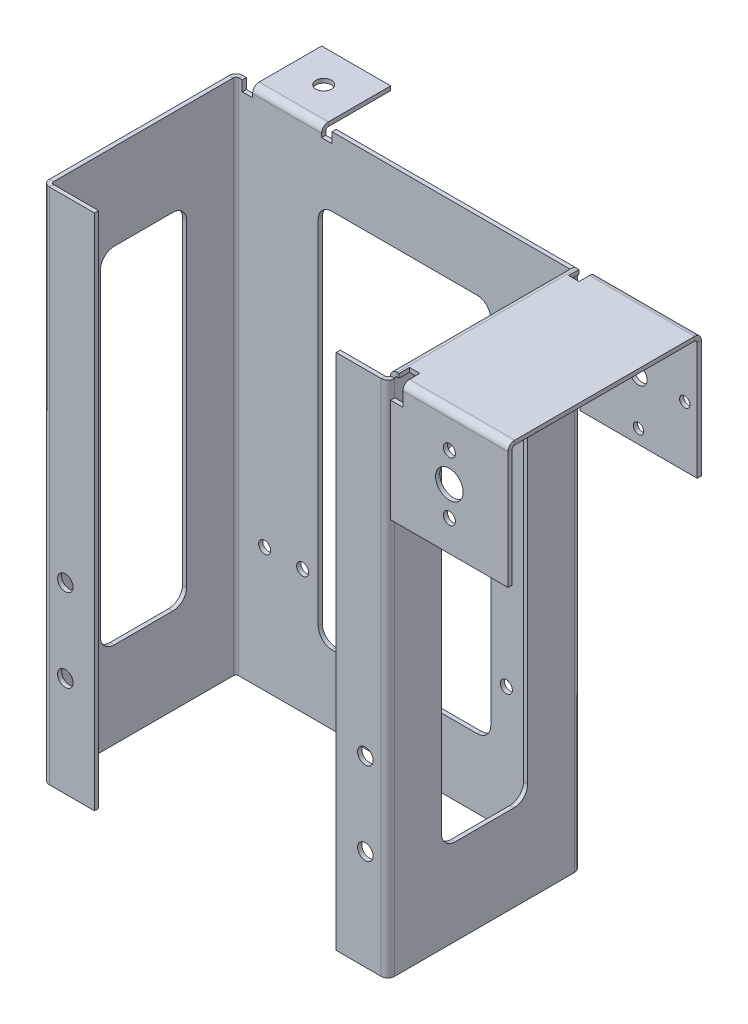
SolidWorks part; units mm, degrees
note: The reader was unsure of these and kept them because the rebuilt part matched: flange length of "Ребро-кромка1", "Ребро-кромка2", "Ребро-кромка3", "Ребро-кромка4", "Ребро-кромка5".
material "Простая углеродистая сталь"
ref_plane "Спереди" through (0, 0, 0) normal (0, 0, 1) x (1, 0, 0)
ref_plane "Сверху" through (0, 0, 0) normal (0, 1, 0) x (1, 0, 0)
ref_plane "Справа" through (0, 0, 0) normal (1, 0, 0) x (0, 0, -1)
sketch "Эскиз1" plane through (0, 0, 0) normal (0, 0, 1) x (1, 0, 0)
  line L1 (0, 0) -> (100, 0)
  line L2 (0, 0) -> (0, 150)
  line L3 (0, 150) -> (100, 150)
  line L4 (100, 0) -> (100, 150)
  dimension "D1" = 150
  dimension "D2" = 100
base flange "Базовая кромка1" sketch "Эскиз1" thickness 1.2 reverse thickness direction no parameters "D1"=0.7366
edge flange "Ребро-кромка1" sketch "Эскиз11" flange profiles "Эскиз11", "Эскиз12" flange angle 90 flange length 56 flange position material inside bend radius 0.7366 thickness 1.2 relief rectangular parameters "D6"=10, "D8"=1
sketch "Эскиз11" plane through (100, 0, 0) normal (1, 0, 0) x (0, 1, 0)
  line L2 (0, 0) -> (0, 54.8)
  line L3 (0, 54.8) -> (150, 54.8)
  line L4 (150, 54.8) -> (150, 0)
  line L5 (0, 0) -> (150, 0) construction
  line L6 (0, 0) -> (150, 0)
sketch "Эскиз12" plane through (0, 0, 0) normal (-1, 0, 0) x (0, -1, 0)
  line L0 (-150, 0) -> (0, 0) construction
  line L1 (-150, 0) -> (0, 0)
  line L2 (-150, 0) -> (-150, 54.8)
  line L3 (-150, 54.8) -> (0, 54.8)
  line L4 (0, 54.8) -> (0, 0)
bend "EdgeBend1" bend radius 0.7366 bend angle 90 parameters "D5"=1
bend "EdgeBend2" bend radius 0.7366 bend angle 90 parameters "D5"=2
edge flange "Ребро-кромка2" sketch "Эскиз17" flange profiles "Эскиз17", "Эскиз18" flange angle 90 flange length 15 flange position material inside bend radius 0.7366 thickness 1.2 relief rectangular parameters "D6"=10, "D8"=1
sketch "Эскиз17" plane through (1.2, 0, 54.8) normal (0, 0, 1) x (0, -1, 0)
  line L2 (-150, 0) -> (-150, 13.8)
  line L3 (-150, 13.8) -> (0, 13.8)
  line L4 (0, 13.8) -> (0, 0)
  line L7 (0, 0) -> (-150, 0) construction
  line L8 (0, 0) -> (-150, 0)
sketch "Эскиз18" plane through (98.8, 0, 54.8) normal (0, 0, 1) x (0, 1, 0)
  line L2 (150, 0) -> (150, 13.8)
  line L3 (150, 13.8) -> (0, 13.8)
  line L4 (0, 13.8) -> (0, 0)
  line L6 (150, 0) -> (0, 0) construction
  line L7 (150, 0) -> (0, 0)
bend "EdgeBend3" bend radius 0.7366 bend angle 90 parameters "D5"=3
bend "EdgeBend4" bend radius 0.7366 bend angle 90 parameters "D5"=4
sketch "Эскиз19" plane through (0, 0, -1.2) normal (0, 0, -1) x (-1, 0, 0)
  line L0 (-50, 150) -> (-50, 130) construction
  line L1 (-71, 130) -> (-29, 130)
  line L2 (-75, 126) -> (-75, 24)
  line L3 (-71, 20) -> (-29, 20)
  line L4 (-25, 126) -> (-25, 24)
  line L5 (-98.0634, 150) -> (-1.9366, 150) construction
  line L6 (-1.9366, 0) -> (-98.0634, 0) construction
  arc A0 (-29, 130) -> (-25, 126) centre (-29, 126) cw
  arc A1 (-29, 20) -> (-25, 24) centre (-29, 24) ccw
  arc A2 (-75, 24) -> (-71, 20) centre (-71, 24) ccw
  arc A3 (-71, 130) -> (-75, 126) centre (-71, 126) ccw
  point P14 (-25, 20)
  point P17 (-75, 20)
  dimension "D4" = 4
  dimension "D1" = 20
  dimension "D2" = 20
  dimension "D3" = 50
extrude "Вырез-Вытянуть1" cut sketch "Эскиз19" against normal up to next normal cut yes
sketch "Эскиз20" plane through (100, 0, 0) normal (1, 0, 0) x (0, 0, -1)
  line L0 (-26.8, 150) -> (-26.8, 125) construction
  line L1 (-35.3, 125) -> (-18.3, 125)
  line L2 (-39.3, 121) -> (-39.3, 29)
  line L3 (-35.3, 25) -> (-18.3, 25)
  line L4 (-14.3, 121) -> (-14.3, 29)
  line L5 (-0.7366, 150) -> (-52.8634, 150) construction
  line L6 (-39.3, 75) -> (-52.8634, 75) construction
  line L7 (-52.8634, 150) -> (-52.8634, 0) construction
  arc A0 (-18.3, 25) -> (-14.3, 29) centre (-18.3, 29) ccw
  arc A1 (-18.3, 125) -> (-14.3, 121) centre (-18.3, 121) cw
  arc A2 (-39.3, 29) -> (-35.3, 25) centre (-35.3, 29) ccw
  arc A3 (-35.3, 125) -> (-39.3, 121) centre (-35.3, 121) ccw
  point P14 (-14.3, 25)
  point P19 (-39.3, 25)
  point P22 (-39.3, 125)
  dimension "D3" = 4
  dimension "D1" = 25
  dimension "D2" = 100
extrude "Вырез-Вытянуть2" cut sketch "Эскиз20" against normal through all normal cut yes
sketch "Эскиз21" plane through (0, 0, 54.8) normal (0, 0, 1) x (1, 0, 0)
  line L0 (6.5317, 53) -> (6.5317, 29) construction
  line L1 (50, 0) -> (50, 29) construction
  line L2 (93.4683, 53) -> (93.4683, 29) construction
  line L3 (6.5317, 53) -> (93.4683, 53) construction
  line L4 (1.9366, 0) -> (98.0634, 0) construction
  line L5 (6.5317, 29) -> (93.4683, 29) construction
  circle A0 centre (6.5317, 53) radius 2.25
  circle A1 centre (6.5317, 29) radius 2.25
  circle A2 centre (93.4683, 53) radius 2.25
  circle A3 centre (93.4683, 29) radius 2.25
  dimension "D4" = 4.5
  dimension "D1" = 86.9366
  dimension "D2" = 29
  dimension "D3" = 24
extrude "Вырез-Вытянуть3" cut sketch "Эскиз21" against normal up to next normal cut yes
sketch "Эскиз22" plane through (0, 0, 0) normal (0, 0, 1) x (1, 0, 0)
  line L0 (50, 36) -> (50, 0) construction
  line L1 (1.9366, 0) -> (98.0634, 0) construction
  line L2 (79.5, 36) -> (90.5, 36) construction
  line L3 (79.5, 36) -> (20.5, 36) construction
  line L4 (20.5, 36) -> (9.5, 36) construction
  circle A4 centre (90.5, 36) radius 1.75
  circle A5 centre (79.5, 36) radius 1.75
  circle A6 centre (20.5, 36) radius 1.75
  circle A7 centre (9.5, 36) radius 1.75
  dimension "D5" = 3.5
  dimension "D1" = 59
  dimension "D2" = 36
  dimension "D3" = 11
  dimension "D4" = 11
extrude "Вырез-Вытянуть4" cut sketch "Эскиз22" against normal up to next normal cut yes
edge flange "Ребро-кромка3" sketch "Эскиз25" flange angle 90 flange length 36 flange position bend outside bend radius 0.7366 thickness 1.2 relief rectangular parameters "D6"=10
sketch "Эскиз25" plane through (100, 150, 0) normal (0, 1, 0) x (0, 0, 1)
  line L0 (0.7366, 0) -> (52.8634, 0) construction
  line L1 (0.7366, 0) -> (52.8634, 0)
  line L2 (0.7366, 0) -> (0.7366, 34.8)
  line L3 (0.7366, 34.8) -> (52.8634, 34.8)
  line L4 (52.8634, 34.8) -> (52.8634, 0)
bend "EdgeBend5" bend radius 0.7366 bend angle 90 parameters "D5"=5
sketch "Эскиз26" plane through (0, 151.9366, 0) normal (0, 1, 0) x (1, 0, 0)
  line L0 (134.8, -52.8634) -> (100, -52.8634) construction
  line L1 (104.3, -52.8634) -> (101.3, -52.8634)
  line L2 (104.3, -52.8634) -> (104.3, -49.8634)
  line L3 (104.3, -49.8634) -> (101.3, -49.8634)
  line L4 (101.3, -52.8634) -> (101.3, -49.8634)
  line L5 (134.8, -0.7366) -> (100.7366, -0.7366) construction
  line L6 (101.3, -3.7366) -> (104.3, -3.7366)
  line L7 (101.3, -3.7366) -> (101.3, -0.7366)
  line L8 (101.3, -0.7366) -> (104.3, -0.7366)
  line L9 (104.3, -3.7366) -> (104.3, -0.7366)
  line L10 (98.8, -0.7366) -> (98.8, -52.8634) construction
  dimension "D1" = 3
  dimension "D2" = 2.5
extrude "Вырез-Вытянуть5" cut sketch "Эскиз26" against normal up to next normal cut yes
edge flange "Ребро-кромка4" sketch "Эскиз31" flange profiles "Эскиз31", "Эскиз32" flange angle 90 flange length 36 flange position bend outside bend radius 0.7366 thickness 1.2 relief rectangular parameters "D6"=10, "D8"=1
sketch "Эскиз31" plane through (0, 150.7366, 52.8634) normal (0, 0, 1) x (-1, 0, 0)
  line L0 (-104.3, 0) -> (-134.8, 0) construction
  line L1 (-104.3, 0) -> (-134.8, 0)
  line L2 (-134.8, 0) -> (-134.8, 34.8)
  line L3 (-134.8, 34.8) -> (-104.3, 34.8)
  line L4 (-104.3, 34.8) -> (-104.3, 0)
sketch "Эскиз32" plane through (0, 150.7366, 0.7366) normal (0, 0, -1) x (1, 0, 0)
  line L0 (134.8, 0) -> (104.3, 0) construction
  line L1 (134.8, 0) -> (104.3, 0)
  line L2 (104.3, 0) -> (104.3, 34.8)
  line L3 (104.3, 34.8) -> (134.8, 34.8)
  line L4 (134.8, 34.8) -> (134.8, 0)
bend "EdgeBend6" bend radius 0.7366 bend angle 90 parameters "D5"=6
bend "EdgeBend7" bend radius 0.7366 bend angle 90 parameters "D5"=7
sketch "Эскиз33" plane through (0, 115.9366, 0) normal (0, -1, 0) x (1, 0, 0)
  line L1 (104.3, 54.8) -> (100.8, 54.8)
  line L2 (104.3, 54.8) -> (104.3, 53.6)
  line L3 (104.3, 53.6) -> (100.8, 53.6)
  line L4 (100.8, 54.8) -> (100.8, 53.6)
  line L5 (104.3, -1.2) -> (100.8, -1.2)
  line L6 (104.3, -1.2) -> (104.3, 0)
  line L7 (104.3, 0) -> (100.8, 0)
  line L8 (100.8, -1.2) -> (100.8, 0)
  point P10 (104.3, 53.6)
  point P12 (104.3, 0)
  point P14 (100.7376, 54.2328)
  dimension "D1" = 3.5
extrude "Бобышка-Вытянуть1" add sketch "Эскиз33" against normal blind 30
sketch "Эскиз34" plane through (0, 0, -1.2) normal (0, 0, -1) x (-1, 0, 0)
  line L0 (-134.8, 133.3366) -> (-100.8, 133.3366) construction
  line L1 (-134.8, 150.7366) -> (-134.8, 115.9366) construction
  line L2 (-100.8, 145.9366) -> (-100.8, 115.9366) construction
  line L3 (-117.8, 115.9366) -> (-117.8, 150.7366) construction
  line L4 (-134.8, 115.9366) -> (-100.8, 115.9366) construction
  circle A0 centre (-117.8, 133.3366) radius 2.5
  circle A1 centre (-117.8, 133.3366) radius 13.4 construction
  circle A2 centre (-117.8, 146.7366) radius 1.5
  circle A3 centre (-131.2, 133.3366) radius 1.5
  circle A4 centre (-117.8, 119.9366) radius 1.5
  circle A5 centre (-104.4, 133.3366) radius 1.5
  dimension "D1" = 5
  dimension "D2" = 26.8
  dimension "D3" = 3
extrude "Вырез-Вытянуть6" cut sketch "Эскиз34" against normal up to next normal cut yes
sketch "Эскиз35" plane through (0, 0, 53.6) normal (0, 0, -1) x (-1, 0, 0)
  line L0 (-117.8, 141.8366) -> (-117.8, 124.8366) construction
  circle A0 centre (-117.8, 133.3366) radius 4
  circle A1 centre (-117.8, 141.8366) radius 1.75
  circle A2 centre (-117.8, 124.8366) radius 1.75
  dimension "D2" = 8
  dimension "D3" = 3.5
  dimension "D1" = 17
extrude "Вырез-Вытянуть7" cut sketch "Эскиз35" against normal up to next normal cut yes
sketch "Эскиз36" plane through (0, 0, -1.2) normal (0, 0, -1) x (-1, 0, 0)
  line L0 (0, 150) -> (-100, 150) construction
  line L1 (-3, 150) -> (-6, 150)
  line L2 (-3, 150) -> (-3, 147)
  line L3 (-3, 147) -> (-6, 147)
  line L4 (-6, 150) -> (-6, 147)
  line L5 (-98.0634, 150) -> (-1.9366, 150) construction
  line L6 (-26, 150) -> (-29, 150)
  line L7 (-26, 150) -> (-26, 147)
  line L8 (-26, 147) -> (-29, 147)
  line L9 (-29, 150) -> (-29, 147)
  line L10 (0, 0) -> (0, 150) construction
  point P14 (-27.5, 147)
  dimension "D1" = 3
  dimension "D2" = 3
  dimension "D3" = 20
extrude "Вырез-Вытянуть8" cut sketch "Эскиз36" against normal up to next normal cut yes
edge flange "Ребро-кромка5" sketch "Эскиз39" flange angle 90 flange length 20 flange position material inside bend radius 0.7366 thickness 1.2 relief rectangular parameters "D6"=10
sketch "Эскиз39" plane through (0, 150, -1.2) normal (0, 1, 0) x (1, 0, 0)
  line L2 (6, 0) -> (6, 18.8)
  line L3 (6, 18.8) -> (26, 18.8)
  line L4 (26, 18.8) -> (26, 0)
  line L5 (26, 0) -> (6, 0) construction
  line L6 (26, 0) -> (6, 0)
bend "EdgeBend8" bend radius 0.7366 bend angle 90 parameters "D5"=8
sketch "Эскиз40" plane through (0, 150, 0) normal (0, 1, 0) x (1, 0, 0)
  line L0 (6, 10.6) -> (26, 10.6) construction
  line L1 (6, 1.2) -> (6, 20) construction
  line L2 (26, 1.9366) -> (26, 20) construction
  circle A0 centre (16, 10.6) radius 2.25
  dimension "D1" = 4.5
extrude "Вырез-Вытянуть9" cut sketch "Эскиз40" against normal up to next normal cut yes
sketch "Сгиб-Линии1" [suppressed] plane through (0, 0, 0) normal (0, 1, 0) x (1, 0, 0)
sketch "Граничная рамка1" [suppressed] plane through (0, 0, 0) normal (0, 1, 0) x (1, 0, 0)
sheet metal parameters "Листовой металл3" thickness 1.2 parameters "D1"=0.7366
flat pattern "Развертка3" [suppressed]
sketch "Сгиб-Линии2" plane through (0, 0, 0) normal (0, 1, 0) x (1, 0, 0)
sketch "Граничная рамка2" [suppressed] plane through (0, 0, 0) normal (0, 1, 0) x (1, 0, 0)
sheet metal parameters "Листовой металл4" thickness 1.2 parameters "D1"=0.7366
flat pattern "Развертка3" [suppressed]
sketch "Сгиб-Линии2" plane through (0, 0, 0) normal (0, 1, 0) x (1, 0, 0)
sketch "Граничная рамка2" [suppressed] plane through (0, 0, 0) normal (0, 1, 0) x (1, 0, 0)
bend of the flat pattern "Плоское состояние-<EdgeBend1>1"
bend of the flat pattern "Плоское состояние-<EdgeBend2>1"
sheet metal parameters "Листовой металл5" thickness 1.2 parameters "D1"=0.7366
flat pattern "Развертка3" [suppressed]
sketch "Сгиб-Линии2" plane through (0, 0, 0) normal (0, 1, 0) x (1, 0, 0)
sketch "Граничная рамка2" [suppressed] plane through (0, 0, 0) normal (0, 1, 0) x (1, 0, 0)
bend of the flat pattern "Плоское состояние-<EdgeBend1>1"
bend of the flat pattern "Плоское состояние-<EdgeBend2>1"
bend of the flat pattern "Плоское состояние-<EdgeBend3>1"
bend of the flat pattern "Плоское состояние-<EdgeBend4>1"
sheet metal parameters "Листовой металл6" thickness 1.2 parameters "D1"=0.7366
flat pattern "Развертка3" [suppressed]
sketch "Сгиб-Линии2" plane through (0, 0, 0) normal (0, 1, 0) x (1, 0, 0)
sketch "Граничная рамка2" [suppressed] plane through (0, 0, 0) normal (0, 1, 0) x (1, 0, 0)
bend of the flat pattern "Плоское состояние-<EdgeBend1>1"
bend of the flat pattern "Плоское состояние-<EdgeBend2>1"
bend of the flat pattern "Плоское состояние-<EdgeBend3>1"
bend of the flat pattern "Плоское состояние-<EdgeBend4>1"
sheet metal parameters "Листовой металл7" thickness 1.2 parameters "D1"=0.7366
flat pattern "Развертка3" [suppressed]
sketch "Сгиб-Линии2" plane through (0, 0, 0) normal (0, 1, 0) x (1, 0, 0)
sketch "Граничная рамка2" [suppressed] plane through (0, 0, 0) normal (0, 1, 0) x (1, 0, 0)
bend of the flat pattern "Плоское состояние-<EdgeBend1>1"
bend of the flat pattern "Плоское состояние-<EdgeBend2>1"
bend of the flat pattern "Плоское состояние-<EdgeBend3>1"
bend of the flat pattern "Плоское состояние-<EdgeBend4>1"
sheet metal parameters "Листовой металл8" thickness 1.2 parameters "D1"=0.7366
flat pattern "Развертка3" [suppressed]
sketch "Сгиб-Линии2" plane through (0, 0, 0) normal (0, 1, 0) x (1, 0, 0)
sketch "Граничная рамка2" [suppressed] plane through (0, 0, 0) normal (0, 1, 0) x (1, 0, 0)
bend of the flat pattern "Плоское состояние-<EdgeBend1>1"
bend of the flat pattern "Плоское состояние-<EdgeBend2>1"
bend of the flat pattern "Плоское состояние-<EdgeBend3>1"
bend of the flat pattern "Плоское состояние-<EdgeBend4>1"
sheet metal parameters "Листовой металл9" thickness 1.2 parameters "D1"=0.7366
flat pattern "Развертка3" [suppressed]
sketch "Сгиб-Линии2" plane through (0, 0, 0) normal (0, 1, 0) x (1, 0, 0)
sketch "Граничная рамка2" [suppressed] plane through (0, 0, 0) normal (0, 1, 0) x (1, 0, 0)
bend of the flat pattern "Плоское состояние-<EdgeBend1>1"
bend of the flat pattern "Плоское состояние-<EdgeBend2>1"
bend of the flat pattern "Плоское состояние-<EdgeBend3>1"
bend of the flat pattern "Плоское состояние-<EdgeBend4>1"
sheet metal parameters "Листовой металл10" thickness 1.2 parameters "D1"=0.7366
flat pattern "Развертка3" [suppressed]
sketch "Сгиб-Линии2" plane through (0, 0, 0) normal (0, 1, 0) x (1, 0, 0)
sketch "Граничная рамка2" [suppressed] plane through (0, 0, 0) normal (0, 1, 0) x (1, 0, 0)
bend of the flat pattern "Плоское состояние-<EdgeBend1>1"
bend of the flat pattern "Плоское состояние-<EdgeBend2>1"
bend of the flat pattern "Плоское состояние-<EdgeBend3>1"
bend of the flat pattern "Плоское состояние-<EdgeBend4>1"
bend of the flat pattern "Плоское состояние-<EdgeBend5>1"
sheet metal parameters "Листовой металл11" thickness 1.2 parameters "D1"=0.7366
flat pattern "Развертка3" [suppressed]
sketch "Сгиб-Линии2" plane through (0, 0, 0) normal (0, 1, 0) x (1, 0, 0)
sketch "Граничная рамка2" [suppressed] plane through (0, 0, 0) normal (0, 1, 0) x (1, 0, 0)
bend of the flat pattern "Плоское состояние-<EdgeBend1>1"
bend of the flat pattern "Плоское состояние-<EdgeBend2>1"
bend of the flat pattern "Плоское состояние-<EdgeBend3>1"
bend of the flat pattern "Плоское состояние-<EdgeBend4>1"
bend of the flat pattern "Плоское состояние-<EdgeBend5>1"
sheet metal parameters "Листовой металл12" thickness 1.2 parameters "D1"=0.7366
flat pattern "Развертка3" [suppressed]
sketch "Сгиб-Линии2" plane through (0, 0, 0) normal (0, 1, 0) x (1, 0, 0)
sketch "Граничная рамка2" [suppressed] plane through (0, 0, 0) normal (0, 1, 0) x (1, 0, 0)
bend of the flat pattern "Плоское состояние-<EdgeBend1>1"
bend of the flat pattern "Плоское состояние-<EdgeBend2>1"
bend of the flat pattern "Плоское состояние-<EdgeBend3>1"
bend of the flat pattern "Плоское состояние-<EdgeBend4>1"
bend of the flat pattern "Плоское состояние-<EdgeBend5>1"
bend of the flat pattern "Плоское состояние-<EdgeBend6>1"
bend of the flat pattern "Плоское состояние-<EdgeBend7>1"
sheet metal parameters "Листовой металл13" thickness 1.2 parameters "D1"=0.7366
flat pattern "Развертка3"
sketch "Сгиб-Линии2" plane through (0, 0, 0) normal (0, 0, 1) x (1, 0, 0)
  line L0 (99.1132, 180.1629) -> (99.1132, 155.6629) construction
  line L1 (153.3395, 155.6629) -> (153.3395, 180.1629) construction
  line L2 (152.2897, 151.0498) -> (100.1629, 151.0498) construction
  line L3 (153.3395, 0) -> (153.3395, 150) construction
  line L4 (-53.3395, 150) -> (-53.3395, 0) construction
  line L5 (0.8868, 150) -> (0.8868, 0) construction
  line L6 (99.1132, 0) -> (99.1132, 150) construction
  line L7 (99.1132, 180.1629) -> (99.1132, 155.6629) construction
  line L8 (153.3395, 155.6629) -> (153.3395, 180.1629) construction
  line L9 (152.2897, 151.0498) -> (100.1629, 151.0498) construction
  line L10 (153.3395, 0) -> (153.3395, 150) construction
  line L11 (-53.3395, 150) -> (-53.3395, 0) construction
  line L12 (0.8868, 150) -> (0.8868, 0) construction
  line L13 (99.1132, 0) -> (99.1132, 150) construction
sketch3d "Граничная рамка2" [suppressed]
  line L0 (-67.4527, 0, 0) -> (182.4527, 0, 0) construction
  line L1 (-67.4527, 180.1629, 0) -> (182.4527, 180.1629, 0) construction
  line L2 (-67.4527, 0, 0) -> (-67.4527, 180.1629, 0) construction
  line L3 (182.4527, 0, 0) -> (182.4527, 180.1629, 0) construction
bend of the flat pattern "Плоское состояние-<EdgeBend1>1"
bend of the flat pattern "Плоское состояние-<EdgeBend2>1"
bend of the flat pattern "Плоское состояние-<EdgeBend3>1"
bend of the flat pattern "Плоское состояние-<EdgeBend4>1"
bend of the flat pattern "Плоское состояние-<EdgeBend5>1"
bend of the flat pattern "Плоское состояние-<EdgeBend6>1"
bend of the flat pattern "Плоское состояние-<EdgeBend7>1"
sheet metal parameters "Листовой металл14" thickness 1.2 parameters "D1"=0.7366
flat pattern "Развертка3"
sketch "Сгиб-Линии2" plane through (0, 0, 0) normal (0, 0, 1) x (1, 0, 0)
  line L0 (99.1132, 180.1629) -> (99.1132, 155.6629) construction
  line L1 (153.3395, 155.6629) -> (153.3395, 180.1629) construction
  line L2 (152.2897, 151.0498) -> (100.1629, 151.0498) construction
  line L3 (153.3395, 0) -> (153.3395, 150) construction
  line L4 (-53.3395, 150) -> (-53.3395, 0) construction
  line L5 (0.8868, 150) -> (0.8868, 0) construction
  line L6 (99.1132, 0) -> (99.1132, 150) construction
  line L7 (99.1132, 180.1629) -> (99.1132, 155.6629) construction
  line L8 (153.3395, 155.6629) -> (153.3395, 180.1629) construction
  line L9 (152.2897, 151.0498) -> (100.1629, 151.0498) construction
  line L10 (153.3395, 0) -> (153.3395, 150) construction
  line L11 (-53.3395, 150) -> (-53.3395, 0) construction
  line L12 (0.8868, 150) -> (0.8868, 0) construction
  line L13 (99.1132, 0) -> (99.1132, 150) construction
sketch3d "Граничная рамка2" [suppressed]
  line L0 (-67.4527, 0, 0) -> (182.4527, 0, 0) construction
  line L1 (-67.4527, 180.1629, 0) -> (182.4527, 180.1629, 0) construction
  line L2 (-67.4527, 0, 0) -> (-67.4527, 180.1629, 0) construction
  line L3 (182.4527, 0, 0) -> (182.4527, 180.1629, 0) construction
bend of the flat pattern "Плоское состояние-<EdgeBend1>1"
bend of the flat pattern "Плоское состояние-<EdgeBend2>1"
bend of the flat pattern "Плоское состояние-<EdgeBend3>1"
bend of the flat pattern "Плоское состояние-<EdgeBend4>1"
bend of the flat pattern "Плоское состояние-<EdgeBend5>1"
bend of the flat pattern "Плоское состояние-<EdgeBend6>1"
bend of the flat pattern "Плоское состояние-<EdgeBend7>1"
sheet metal parameters "Листовой металл15" thickness 1.2 parameters "D1"=0.7366
flat pattern "Развертка3"
sketch "Сгиб-Линии2" plane through (0, 0, 0) normal (0, 0, 1) x (1, 0, 0)
  line L0 (99.1132, 180.1629) -> (99.1132, 155.6629) construction
  line L1 (153.3395, 155.6629) -> (153.3395, 180.1629) construction
  line L2 (152.2897, 151.0498) -> (100.1629, 151.0498) construction
  line L3 (153.3395, 0) -> (153.3395, 150) construction
  line L4 (-53.3395, 150) -> (-53.3395, 0) construction
  line L5 (0.8868, 150) -> (0.8868, 0) construction
  line L6 (99.1132, 0) -> (99.1132, 150) construction
  line L7 (99.1132, 180.1629) -> (99.1132, 155.6629) construction
  line L8 (153.3395, 155.6629) -> (153.3395, 180.1629) construction
  line L9 (152.2897, 151.0498) -> (100.1629, 151.0498) construction
  line L10 (153.3395, 0) -> (153.3395, 150) construction
  line L11 (-53.3395, 150) -> (-53.3395, 0) construction
  line L12 (0.8868, 150) -> (0.8868, 0) construction
  line L13 (99.1132, 0) -> (99.1132, 150) construction
sketch3d "Граничная рамка2" [suppressed]
  line L0 (-67.4527, 0, 0) -> (182.4527, 0, 0) construction
  line L1 (-67.4527, 180.1629, 0) -> (182.4527, 180.1629, 0) construction
  line L2 (-67.4527, 0, 0) -> (-67.4527, 180.1629, 0) construction
  line L3 (182.4527, 0, 0) -> (182.4527, 180.1629, 0) construction
bend of the flat pattern "Плоское состояние-<EdgeBend1>1"
bend of the flat pattern "Плоское состояние-<EdgeBend2>1"
bend of the flat pattern "Плоское состояние-<EdgeBend3>1"
bend of the flat pattern "Плоское состояние-<EdgeBend4>1"
bend of the flat pattern "Плоское состояние-<EdgeBend5>1"
bend of the flat pattern "Плоское состояние-<EdgeBend6>1"
bend of the flat pattern "Плоское состояние-<EdgeBend7>1"
sheet metal parameters "Листовой металл16" thickness 1.2 parameters "D1"=0.7366
flat pattern "Развертка3"
sketch "Сгиб-Линии2" plane through (0, 0, 0) normal (0, 0, 1) x (1, 0, 0)
  line L0 (99.1132, 180.1629) -> (99.1132, 155.6629) construction
  line L1 (153.3395, 155.6629) -> (153.3395, 180.1629) construction
  line L2 (152.2897, 151.0498) -> (100.1629, 151.0498) construction
  line L3 (153.3395, 0) -> (153.3395, 150) construction
  line L4 (-53.3395, 150) -> (-53.3395, 0) construction
  line L5 (0.8868, 150) -> (0.8868, 0) construction
  line L6 (99.1132, 0) -> (99.1132, 150) construction
  line L7 (99.1132, 180.1629) -> (99.1132, 155.6629) construction
  line L8 (153.3395, 155.6629) -> (153.3395, 180.1629) construction
  line L9 (152.2897, 151.0498) -> (100.1629, 151.0498) construction
  line L10 (153.3395, 0) -> (153.3395, 150) construction
  line L11 (-53.3395, 150) -> (-53.3395, 0) construction
  line L12 (0.8868, 150) -> (0.8868, 0) construction
  line L13 (99.1132, 0) -> (99.1132, 150) construction
sketch3d "Граничная рамка2" [suppressed]
  line L0 (-67.4527, 0, 0) -> (182.4527, 0, 0) construction
  line L1 (-67.4527, 180.1629, 0) -> (182.4527, 180.1629, 0) construction
  line L2 (-67.4527, 0, 0) -> (-67.4527, 180.1629, 0) construction
  line L3 (182.4527, 0, 0) -> (182.4527, 180.1629, 0) construction
bend of the flat pattern "Плоское состояние-<EdgeBend1>1"
bend of the flat pattern "Плоское состояние-<EdgeBend2>1"
bend of the flat pattern "Плоское состояние-<EdgeBend3>1"
bend of the flat pattern "Плоское состояние-<EdgeBend4>1"
bend of the flat pattern "Плоское состояние-<EdgeBend5>1"
bend of the flat pattern "Плоское состояние-<EdgeBend6>1"
bend of the flat pattern "Плоское состояние-<EdgeBend7>1"
sheet metal parameters "Листовой металл17" thickness 1.2 parameters "D1"=0.7366
flat pattern "Развертка3" [suppressed]
sketch "Сгиб-Линии2" plane through (0, 0, 0) normal (0, 0, 1) x (1, 0, 0)
  line L0 (99.1132, 180.1629) -> (99.1132, 155.6629) construction
  line L1 (153.3395, 155.6629) -> (153.3395, 180.1629) construction
  line L2 (152.2897, 151.0498) -> (100.1629, 151.0498) construction
  line L3 (153.3395, 0) -> (153.3395, 150) construction
  line L4 (-53.3395, 150) -> (-53.3395, 0) construction
  line L5 (0.8868, 150) -> (0.8868, 0) construction
  line L6 (99.1132, 0) -> (99.1132, 150) construction
  line L7 (99.1132, 180.1629) -> (99.1132, 155.6629) construction
  line L8 (153.3395, 155.6629) -> (153.3395, 180.1629) construction
  line L9 (152.2897, 151.0498) -> (100.1629, 151.0498) construction
  line L10 (153.3395, 0) -> (153.3395, 150) construction
  line L11 (-53.3395, 150) -> (-53.3395, 0) construction
  line L12 (0.8868, 150) -> (0.8868, 0) construction
  line L13 (99.1132, 0) -> (99.1132, 150) construction
sketch3d "Граничная рамка2" [suppressed]
  line L0 (-67.4527, 0, 0) -> (182.4527, 0, 0) construction
  line L1 (-67.4527, 180.1629, 0) -> (182.4527, 180.1629, 0) construction
  line L2 (-67.4527, 0, 0) -> (-67.4527, 180.1629, 0) construction
  line L3 (182.4527, 0, 0) -> (182.4527, 180.1629, 0) construction
bend of the flat pattern "Плоское состояние-<EdgeBend1>1"
bend of the flat pattern "Плоское состояние-<EdgeBend2>1"
bend of the flat pattern "Плоское состояние-<EdgeBend3>1"
bend of the flat pattern "Плоское состояние-<EdgeBend4>1"
bend of the flat pattern "Плоское состояние-<EdgeBend5>1"
bend of the flat pattern "Плоское состояние-<EdgeBend6>1"
bend of the flat pattern "Плоское состояние-<EdgeBend7>1"
bend of the flat pattern "Плоское состояние-<EdgeBend8>1"
sheet metal parameters "Листовой металл18" thickness 1.2 parameters "D1"=0.7366
flat pattern "Развертка3" [suppressed]
sketch "Сгиб-Линии2" plane through (0, 0, 0) normal (0, 0, 1) x (1, 0, 0)
  line L0 (99.1132, 180.1629) -> (99.1132, 155.6629) construction
  line L1 (153.3395, 155.6629) -> (153.3395, 180.1629) construction
  line L2 (152.2897, 151.0498) -> (100.1629, 151.0498) construction
  line L3 (153.3395, 0) -> (153.3395, 150) construction
  line L4 (-53.3395, 150) -> (-53.3395, 0) construction
  line L5 (0.8868, 150) -> (0.8868, 0) construction
  line L6 (99.1132, 0) -> (99.1132, 150) construction
  line L7 (99.1132, 180.1629) -> (99.1132, 155.6629) construction
  line L8 (153.3395, 155.6629) -> (153.3395, 180.1629) construction
  line L9 (152.2897, 151.0498) -> (100.1629, 151.0498) construction
  line L10 (153.3395, 0) -> (153.3395, 150) construction
  line L11 (-53.3395, 150) -> (-53.3395, 0) construction
  line L12 (0.8868, 150) -> (0.8868, 0) construction
  line L13 (99.1132, 0) -> (99.1132, 150) construction
sketch3d "Граничная рамка2" [suppressed]
  line L0 (-67.4527, 0, 0) -> (182.4527, 0, 0) construction
  line L1 (-67.4527, 180.1629, 0) -> (182.4527, 180.1629, 0) construction
  line L2 (-67.4527, 0, 0) -> (-67.4527, 180.1629, 0) construction
  line L3 (182.4527, 0, 0) -> (182.4527, 180.1629, 0) construction
bend of the flat pattern "Плоское состояние-<EdgeBend1>1"
bend of the flat pattern "Плоское состояние-<EdgeBend2>1"
bend of the flat pattern "Плоское состояние-<EdgeBend3>1"
bend of the flat pattern "Плоское состояние-<EdgeBend4>1"
bend of the flat pattern "Плоское состояние-<EdgeBend5>1"
bend of the flat pattern "Плоское состояние-<EdgeBend6>1"
bend of the flat pattern "Плоское состояние-<EdgeBend7>1"
bend of the flat pattern "Плоское состояние-<EdgeBend8>1"
